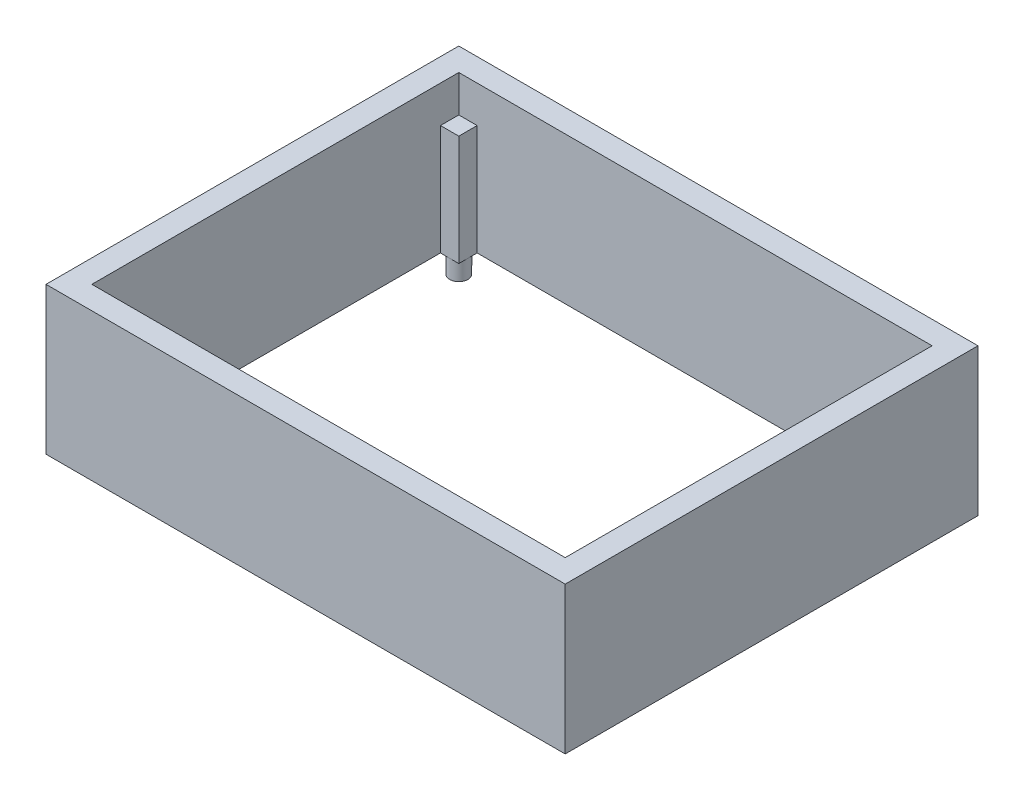
SolidWorks part; units mm, degrees
ref_plane "Front Plane" through (0, 0, 0) normal (0, 0, 1) x (1, 0, 0)
ref_plane "Top Plane" through (0, 0, 0) normal (0, 1, 0) x (1, 0, 0)
ref_plane "Right Plane" through (0, 0, 0) normal (1, 0, 0) x (0, 0, -1)
sketch "Sketch1" plane through (0, 0, 0) normal (0, 1, 0) x (1, 0, 0)
  line L1 (0, 0) -> (283, 0)
  line L2 (0, 0) -> (0, 225)
  line L3 (0, 225) -> (283, 225)
  line L4 (283, 0) -> (283, 225)
  dimension "D1" = 225
  dimension "D2" = 283
extrude "Boss-Extrude1" add sketch "Sketch1" along normal blind 80.2 contours L1 L4 L3 L2
sketch "Sketch2" plane through (0, 80.2, 0) normal (0, 1, 0) x (1, 0, 0)
  line L14 (12.5, 12.5) -> (270.5, 12.5)
  line L15 (270.5, 12.5) -> (270.5, 212.5)
  line L16 (270.5, 212.5) -> (12.5, 212.5)
  line L17 (12.5, 212.5) -> (12.5, 12.5)
  line L18 (12.5, 12.5) -> (270.5, 12.5)
  line L19 (270.5, 12.5) -> (270.5, 212.5)
  line L20 (270.5, 212.5) -> (12.5, 212.5)
  line L21 (12.5, 212.5) -> (12.5, 12.5)
  dimension "D1" = 12.5
extrude "Cut-Extrude1" cut sketch "Sketch2" against normal up to surface (80.2 mm away) contours L21 L18 L19 L20 up to face at (141.5, 0, -112.5)
sketch "Sketch3" plane through (0, 0, 0) normal (0, -1, 0) x (1, 0, 0)
  line L1 (12.5, -12.5) -> (22.5, -12.5)
  line L2 (12.5, -12.5) -> (12.5, -22.5)
  line L3 (12.5, -22.5) -> (22.5, -22.5)
  line L4 (22.5, -12.5) -> (22.5, -22.5)
  line L5 (12.5, -212.5) -> (22.5, -212.5)
  line L6 (12.5, -212.5) -> (12.5, -202.5)
  line L7 (12.5, -202.5) -> (22.5, -202.5)
  line L8 (22.5, -212.5) -> (22.5, -202.5)
  line L9 (270.5, -212.5) -> (260.5, -212.5)
  line L10 (270.5, -212.5) -> (270.5, -202.5)
  line L11 (270.5, -202.5) -> (260.5, -202.5)
  line L12 (260.5, -212.5) -> (260.5, -202.5)
  line L13 (270.5, -12.5) -> (260.5, -12.5)
  line L14 (270.5, -12.5) -> (270.5, -22.5)
  line L15 (270.5, -22.5) -> (260.5, -22.5)
  line L16 (260.5, -12.5) -> (260.5, -22.5)
  dimension "D1" = 10
  dimension "D2" = 10
  dimension "D3" = 10
  dimension "D4" = 10
  dimension "D5" = 10
  dimension "D6" = 10
  dimension "D7" = 10
  dimension "D8" = 10
extrude "Boss-Extrude2" add sketch "Sketch3" against normal blind 60.16
sketch "Sketch4" plane through (0, 0, 0) normal (0, -1, 0) x (1, 0, 0)
  line L0 (17.5, -202.5) -> (17.5, -207.5) construction
  line L1 (22.5, -202.5) -> (12.5, -202.5) construction
  line L2 (17.5, -207.5) -> (22.5, -207.5) construction
  line L3 (22.5, -212.5) -> (22.5, -202.5) construction
  line L4 (17.5, -22.5) -> (17.5, -17.5) construction
  line L5 (12.5, -22.5) -> (22.5, -22.5) construction
  line L6 (17.5, -17.5) -> (22.5, -17.5) construction
  line L7 (22.5, -22.5) -> (22.5, -12.5) construction
  line L8 (260.5, -207.5) -> (265.5, -207.5) construction
  line L9 (260.5, -202.5) -> (260.5, -212.5) construction
  line L10 (265.5, -207.5) -> (265.5, -202.5) construction
  line L11 (270.5, -202.5) -> (260.5, -202.5) construction
  line L12 (260.5, -22.5) -> (270.5, -22.5) construction
  line L13 (265.5, -22.5) -> (265.5, -17.5) construction
  line L14 (265.5, -17.5) -> (260.5, -17.5) construction
  line L15 (260.5, -12.5) -> (260.5, -22.5) construction
  circle A0 centre (17.5, -17.5) radius 5
  circle A1 centre (265.5, -17.5) radius 5
  circle A2 centre (265.5, -207.5) radius 5
  circle A3 centre (17.5, -207.5) radius 5
  dimension "D1" = 10
  dimension "D2" = 10
  dimension "D3" = 10
  dimension "D4" = 10
extrude "Boss-Extrude3" add sketch "Sketch4" along normal blind 10
equation "\"Length\"= 283mm"
equation "\"Width\"= 225mm"
equation "\"WallThickness\"= 12.5mm"
equation "\"UpperWaterJacketThickness\"= 28mm"
equation "\"D1@Sketch1\"=\"Width\""
equation "\"D2@Sketch1\"=\"Length\""
equation "\"SpacerHeight\"= 80.2mm"
equation "\"D1@Boss-Extrude1\"=\"SpacerHeight\""
equation "\"D1@Sketch2\"=\"WallThickness\""
equation "\"SpacerCornerWidth\"= 10mm"
equation "\"D1@Sketch3\"=\"SpacerCornerWidth\""
equation "\"D2@Sketch3\"=\"SpacerCornerWidth\""
equation "\"D3@Sketch3\"=\"SpacerCornerWidth\""
equation "\"D4@Sketch3\"=\"SpacerCornerWidth\""
equation "\"D5@Sketch3\"=\"SpacerCornerWidth\""
equation "\"D6@Sketch3\"=\"SpacerCornerWidth\""
equation "\"D7@Sketch3\"=\"SpacerCornerWidth\""
equation "\"D8@Sketch3\"=\"SpacerCornerWidth\""
equation "\"SpacerCornerHeight\"= 60.16mm"
equation "\"D1@Boss-Extrude2\"=\"SpacerCornerHeight\""
equation "\"SpacerPegDiameter\"= 10mm"
equation "\"D1@Sketch4\"=\"SpacerPegDiameter\""
equation "\"D2@Sketch4\"=\"SpacerPegDiameter\""
equation "\"D3@Sketch4\"=\"SpacerPegDiameter\""
equation "\"D4@Sketch4\"=\"SpacerPegDiameter\""
equation "\"SpacerPegHeight\"= 10mm"
equation "\"D1@Boss-Extrude3\"=\"SpacerPegHeight\""
